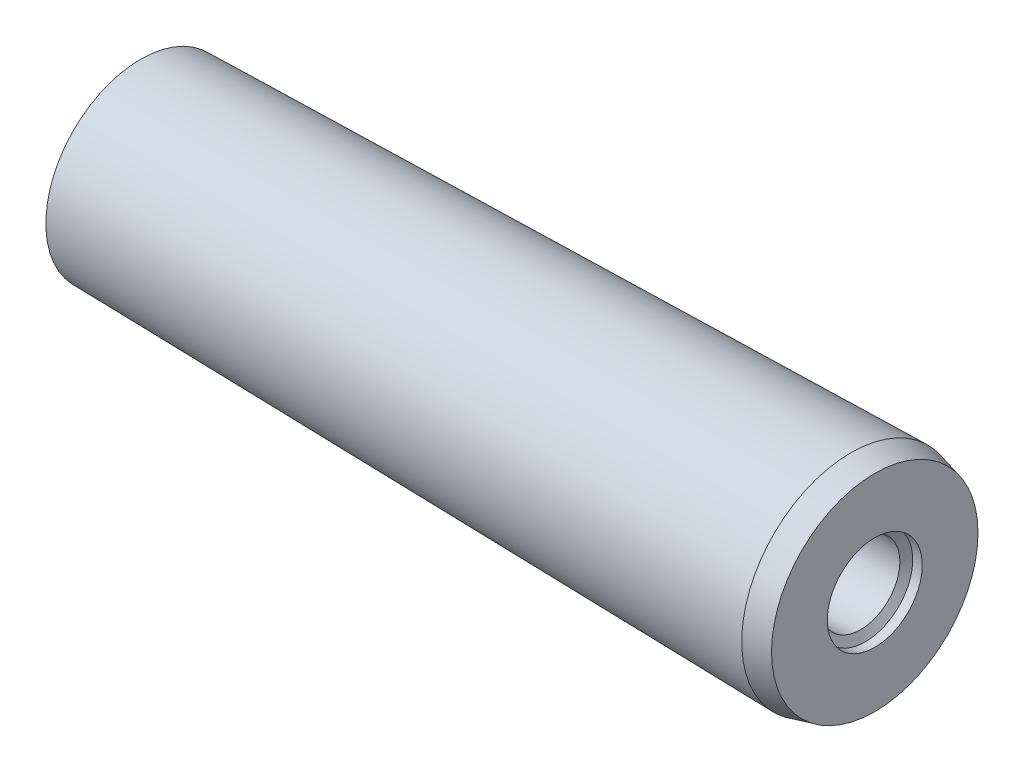
SolidWorks part; units mm, degrees
ref_plane "Front Plane" through (0, 0, 0) normal (0, 0, 1) x (1, 0, 0)
ref_plane "Top Plane" through (0, 0, 0) normal (0, 1, 0) x (1, 0, 0)
ref_plane "Right Plane" through (0, 0, 0) normal (1, 0, 0) x (0, 0, -1)
sketch "BodySke" plane through (0, 0, 0) normal (0, 0, 1) x (1, 0, 0)
  line L0 (0, 0) -> (-250, 0) construction
  line L1 (0, 0) -> (0, 5) construction
  line L2 (0, 5) -> (-250, 0) construction
  line L3 (-200, 0) -> (-55.9767, 0)
  line L4 (-6.3, 28.74) -> (-193.3013, 25)
  line L5 (-193.3013, 25) -> (-193.3013, 0) construction
  line L6 (0, 12.5) -> (-2.5, 12.5)
  line L7 (-2.5, 12.5) -> (-3.7401, 10.352)
  line L8 (-3.7401, 10.352) -> (-50, 10.352)
  line L9 (-50, 10.352) -> (-55.9767, 0)
  line L10 (-2.5, -12.5) -> (-3.7401, -10.352) construction
  line L11 (0, 27.1863) -> (-6.3, 28.74)
  line L12 (0, 12.5) -> (0, 27.1863)
  line L13 (-36, 0) -> (-36, 15.7679) construction
  line L14 (-3, 0) -> (-3, 4.94) construction
  arc A0 (-193.3013, 25) -> (-200, 0) centre (-150, 0) ccw
  point P5 (-36, 12)
  dimension "D1" = 5
  dimension "D2" = 250
  dimension "Advance" = 3
revolve "BaseBody" add sketch "BodySke" angle 360 about L0
cosmetic thread "ThreadCosmetic" [suppressed]
sketch "ThdSchSke" plane through (0, 0, 0) normal (0, 0, 1) x (1, 0, 0)
  line L0 (0, 0) -> (-60.7083, 0) construction
  line L1 (-200, 0) -> (-55.9767, 0) construction
  line L2 (-6.7401, 8.4491) -> (-4.8372, 8.4491)
  line L3 (-4.8372, 8.4491) -> (-4.8372, 10.352)
  line L4 (-6.7401, 8.4491) -> (-6.7401, 10.352)
  line L5 (-6.7401, 10.352) -> (-5.7887, 12)
  line L6 (-5.7887, 12) -> (-4.8372, 10.352)
  line L7 (-3.7401, 10.352) -> (-50, 10.352) construction
  dimension "D1" = 3
revolve "ThreadSchematic" [suppressed] cut sketch "ThdSchSke" angle 360 about L0
pattern_linear "ThdSchPat" [suppressed] of bodies 114
equation "\"D1@ThreadCosmetic\" = \"Thread_length@BodySke\""
equation "\"D2@ThreadCosmetic\" = \"Thread_minor@BodySke\""
equation "\"D1@ThdSchSke\" = \"Advance@BodySke\""
equation "\"Advance@ThdSchPat\" = \"Advance@BodySke\""
equation "\"Tooth_Num@ThdSchPat\" =  int(  ( \"Thread_length@BodySke\" - \"Depth@BodySke\" )  / \"Advance@BodySke\" ) "
equation "\"Round_end@BodySke\" = \"Nominal_dia@BodySke\""
